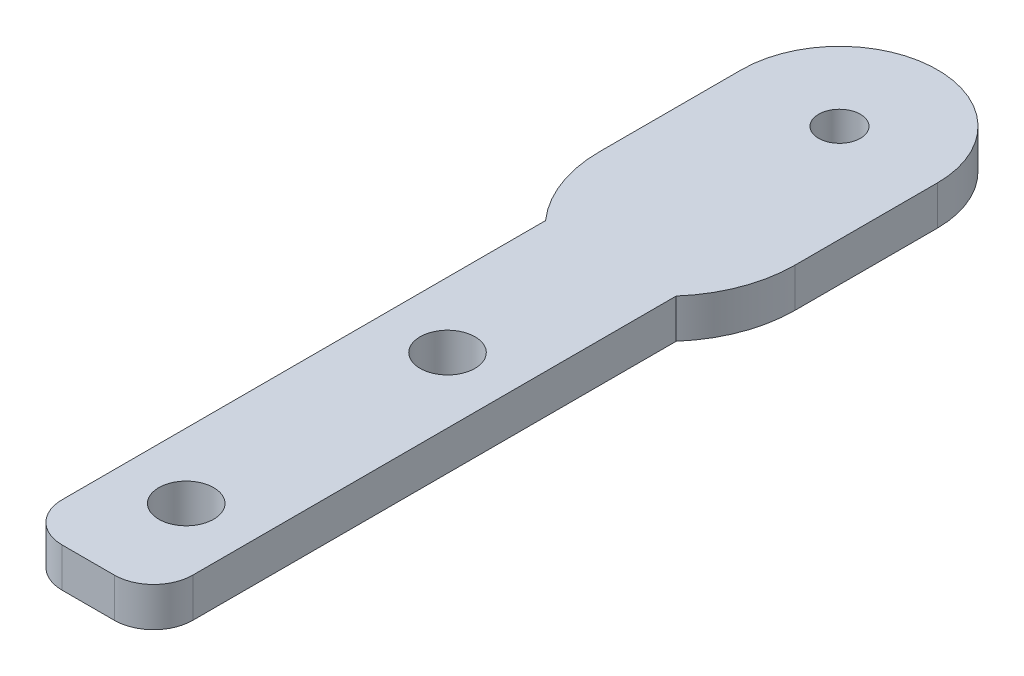
SolidWorks part; units mm, degrees
material "Thornel Mat VMA"
ref_plane "前视基准面" through (0, 0, 0) normal (0, 0, 1) x (1, 0, 0)
ref_plane "上视基准面" through (0, 0, 0) normal (0, 1, 0) x (1, 0, 0)
ref_plane "右视基准面" through (0, 0, 0) normal (1, 0, 0) x (0, 0, -1)
sketch "草图1" plane through (0, 0, 0) normal (0, 1, 0) x (1, 0, 0)
  line L1 (-7.5, -30) -> (7.5, -30)
  line L2 (-7.5, -30) -> (-7.5, 30)
  line L4 (7.5, -30) -> (7.5, 30)
  line L5 (-7.5, -30) -> (7.5, 30) construction
  line L6 (-7.5, 30) -> (7.5, -30) construction
  arc A0 (-7.5, 30) -> (7.5, 30) centre (0, 30) cw
  point P0 (0, 0)
  dimension "D1" = 15
  dimension "D2" = 60
extrude "凸台-拉伸1" add sketch "草图1" along normal blind 3
sketch "草图2" plane through (0, 3, 0) normal (0, 1, 0) x (1, 0, 0)
  circle A0 centre (0, 30) radius 1.6
  dimension "D1" = 3.2
extrude "切除-拉伸1" cut sketch "草图2" against normal blind 3
sketch "草图3" plane through (0, 0, 0) normal (0, -1, 0) x (1, 0, 0)
  line L0 (-7.5, 30) -> (7.5, 30) construction
  circle A0 centre (0, 20) radius 2.1
  circle A1 centre (0, 0) radius 2.1
  dimension "D1" = 4.2
  dimension "D2" = 20
  dimension "D3" = 10
extrude "切除-拉伸2" cut sketch "草图3" against normal blind 3
sketch "草图4" plane through (0, 0, 0) normal (0, -1, 0) x (1, 0, 0)
  line L0 (-7.5, -12.5) -> (-4.9981, -12.5)
  line L1 (-7.5, -30) -> (-7.5, 30) construction
  line L2 (-4.9981, -12.5) -> (-4.9981, 27.5)
  line L4 (-4.9981, 27.5) -> (5.0019, 27.5)
  line L5 (5.0019, 27.5) -> (5.0019, -12.5)
  line L6 (5.0019, -12.5) -> (7.5, -12.5)
  line L7 (7.5, 30) -> (7.5, -30) construction
  line L9 (-7.5, 30) -> (7.5, 30) construction
  line L10 (-7.5, -12.5) -> (-7.5, 30)
  line L11 (-7.5, 30) -> (7.5, 30)
  line L12 (7.5, 30) -> (7.5, -12.5)
  dimension "D1" = 10
  dimension "D2" = 2.4981
  dimension "D3" = 40
  dimension "D4" = 2.5
extrude "切除-拉伸3" cut sketch "草图4" against normal blind 10
fillet "圆角1" radius 10 2 edges at (7.5, 1.5, -12.5) (-7.5, 1.5, -12.5)
fillet "圆角2" radius 3 2 edges at (5.0019, 1.5, 27.5) (-4.9981, 1.5, 27.5)
